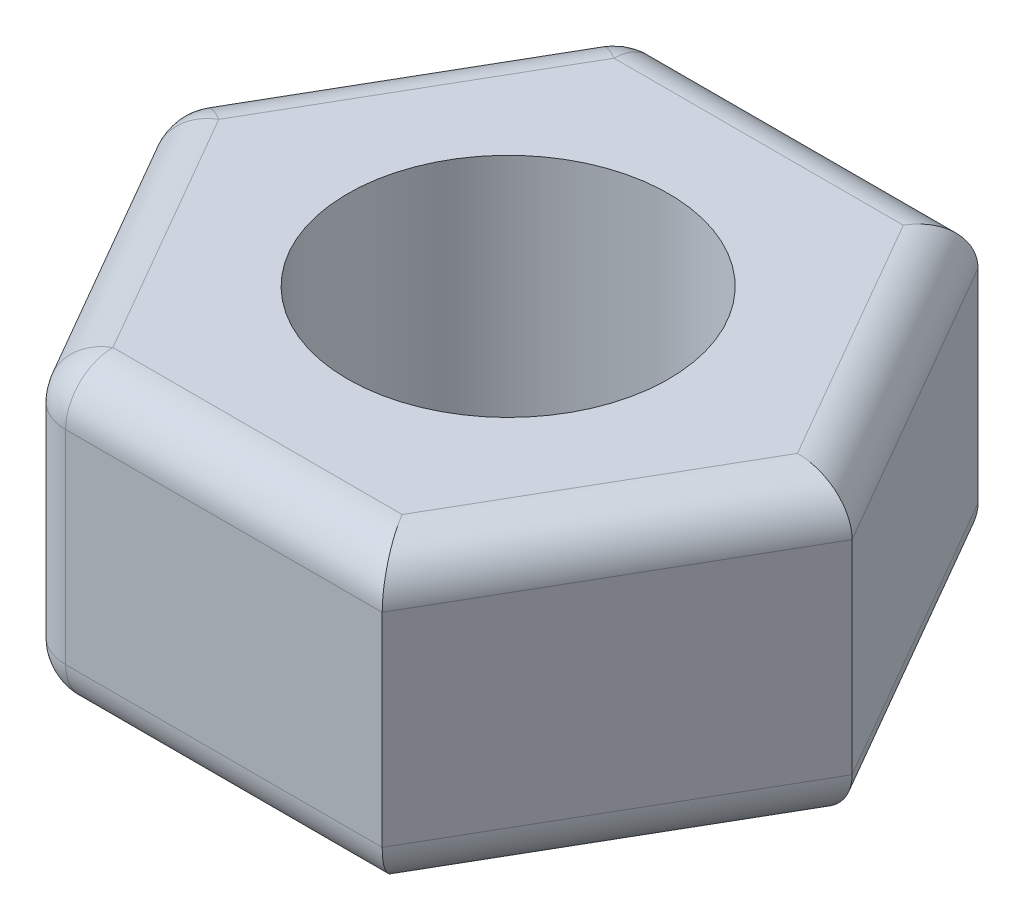
SolidWorks part; units mm, degrees
ref_plane "Front Plane" through (0, 0, 0) normal (0, 0, 1) x (1, 0, 0)
ref_plane "Top Plane" through (0, 0, 0) normal (0, 1, 0) x (1, 0, 0)
ref_plane "Right Plane" through (0, 0, 0) normal (1, 0, 0) x (0, 0, -1)
sketch "Sketch1" plane through (0, 0, 0) normal (0, 1, 0) x (1, 0, 0)
  line L1 (7.2644, 0) -> (3.6322, 6.2912)
  line L2 (3.6322, 6.2912) -> (-3.6322, 6.2912)
  line L3 (-3.6322, 6.2912) -> (-7.2644, 0)
  line L4 (-7.2644, 0) -> (-3.6322, -6.2912)
  line L5 (-3.6322, -6.2912) -> (3.6322, -6.2912)
  line L6 (3.6322, -6.2912) -> (7.2644, 0)
  circle A0 centre (0, 0) radius 6.2912 construction
  dimension "D1" = 14.5288
extrude "Boss-Extrude1" add sketch "Sketch1" along normal blind 6.2992
sketch "Sketch2" plane through (0, 6.2992, 0) normal (0, 1, 0) x (1, 0, 0)
  circle A0 centre (0, 0) radius 3.3909
  dimension "D1" = 6.7818
extrude "Cut-Extrude1" cut sketch "Sketch2" against normal blind 6.2992
fillet "Fillet2" radius 1 1 edges at (-5.4483, 6.2992, 3.1456)
fillet "Fillet3" radius 1 3 edges at (-7.2644, 2.6496, 0) (-7.0953, 6.0063, -0.2929) (-5.1596, 6.2992, -3.6456)
fillet "Fillet4" radius 1 15 edges at (-7.1097, 0, 0) (-3.6322, 2.6496, -6.2912) (-3.294, 6.0063, -6.2912) (-3.6322, 2.6496, 6.2912) (-3.294, 6.0063, 6.2912) (-5.304, 0, 3.3956) (-5.304, 0, -3.3956) (0, 0, -6.2912) (5.4483, 0, -3.1456) (5.4483, 0, 3.1456) (0, 0, 6.2912) (0.5774, 6.2992, -6.2912) (5.4483, 6.2992, -3.1456) (5.4483, 6.2992, 3.1456) (0.5774, 6.2992, 6.2912)
